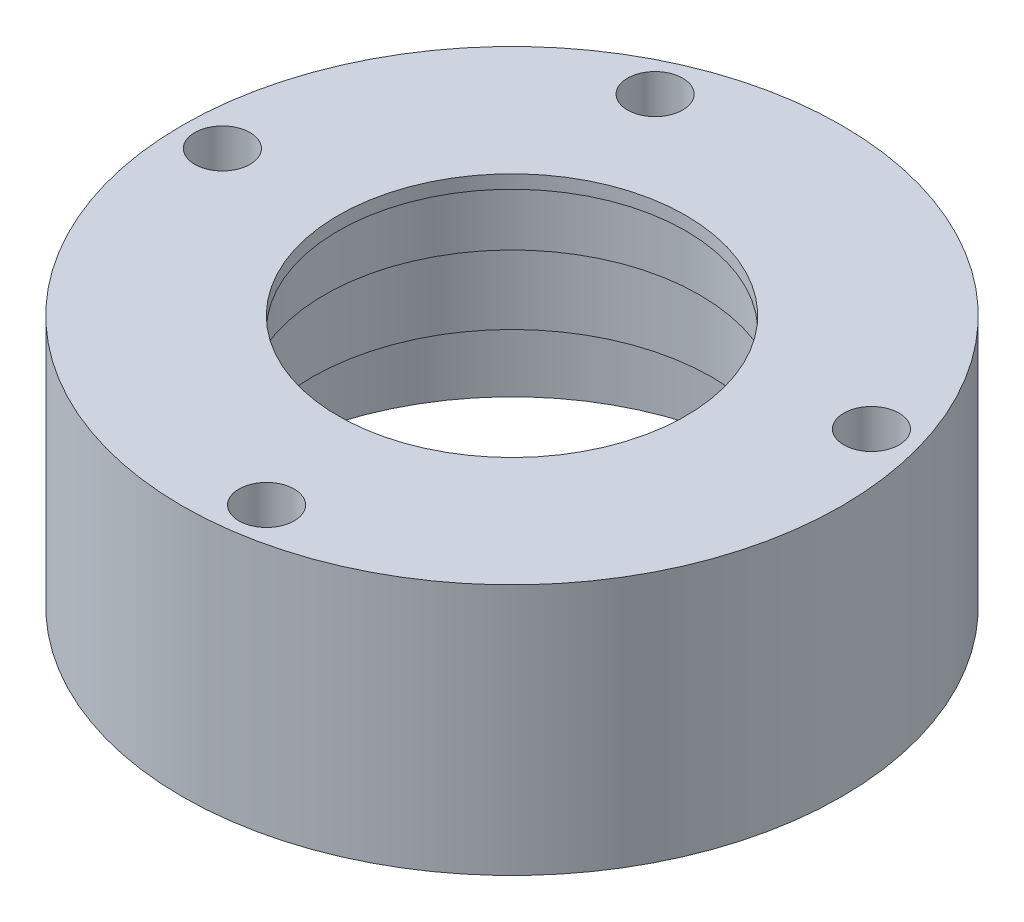
SolidWorks part; units mm, degrees
ref_plane "Front Plane" through (0, 0, 0) normal (0, 0, 1) x (1, 0, 0)
ref_plane "Top Plane" through (0, 0, 0) normal (0, 1, 0) x (1, 0, 0)
ref_plane "Right Plane" through (0, 0, 0) normal (1, 0, 0) x (0, 0, -1)
sketch "Sketch1" plane through (0, 0, 0) normal (0, 1, 0) x (1, 0, 0)
  circle A0 centre (0, 0) radius 37
  dimension "D1" = 74
extrude "Boss-Extrude1" add sketch "Sketch1" along normal blind 28.25
sketch "Sketch2" plane through (0, 0, 0) normal (0, 1, 0) x (1, 0, 0)
  circle A0 centre (0, 0) radius 28.8
  dimension "D1" = 57.6
extrude "Cut-Extrude1" cut sketch "Sketch2" along normal blind 11
sketch "Sketch3" plane through (0, 11, 0) normal (0, -1, 0) x (1, 0, 0)
  circle A0 centre (0, 0) radius 22.5
  dimension "D1" = 45
extrude "Cut-Extrude2" cut sketch "Sketch3" against normal blind 8.75
sketch "Sketch4" plane through (0, 19.75, 0) normal (0, -1, 0) x (1, 0, 0)
  circle A0 centre (0, 0) radius 21.05
  dimension "D1" = 42.1
extrude "Cut-Extrude3" cut sketch "Sketch4" against normal blind 7
sketch "Sketch5" plane through (0, 26.75, 0) normal (0, -1, 0) x (1, 0, 0)
  circle A0 centre (0, 0) radius 19.5
  dimension "D1" = 39
extrude "Cut-Extrude4" cut sketch "Sketch5" against normal through all
sketch "Sketch6" plane through (0, 0, 0) normal (0, 1, 0) x (1, 0, 0)
  line L0 (-15.5375, 0) -> (15.5375, 0) construction
  circle A0 centre (27, 0) radius 1.65
  dimension "D1" = 3.3
  dimension "D2" = 27
extrude "Cut-Extrude5" cut sketch "Sketch6" along normal blind 15.75
pattern_circular "CirPattern1" count 11 over 360 about axis through (0, 28.25, 0) along (0, -1, 0) of "Cut-Extrude5" reverse direction yes
sketch "Sketch7" plane through (0, 0, 0) normal (0, 1, 0) x (1, 0, 0)
  line L0 (0, 0) -> (43.5659, 0) construction
  line L1 (0, 0) -> (39.8091, 11.6863) construction
  line L2 (0, 0) -> (-18.3308, 40.1305) construction
  line L3 (0, 0) -> (-43.804, 0) construction
  line L4 (0, 0) -> (6.4033, -44.546) construction
  circle A0 centre (31.1841, 9.1543) radius 1.7
  circle A1 centre (-13.5033, 29.562) radius 1.7
  circle A2 centre (-32.5, 0) radius 1.7
  circle A3 centre (4.6242, -32.1693) radius 1.7
  dimension "D5" = 3.4
  dimension "D6" = 3.4
  dimension "D7" = 3.4
  dimension "D8" = 3.4
  dimension "D1" = 16.36
  dimension "D2" = 114.55
  dimension "D3" = 180
  dimension "D4" = 278.18
  dimension "D9" = 32.5
  dimension "D10" = 32.5
  dimension "D11" = 32.5
  dimension "D12" = 32.5
extrude "Cut-Extrude6" cut sketch "Sketch7" along normal through all
sketch "Sketch8" plane through (0, 28.25, 0) normal (0, 1, 0) x (1, 0, 0)
  circle A0 centre (31.1841, 9.1543) radius 3.1
  circle A1 centre (-13.5033, 29.562) radius 3.1
  circle A2 centre (-32.5, 0) radius 3.1
  circle A3 centre (4.6242, -32.1693) radius 3.1
  dimension "D1" = 6.2
  dimension "D2" = 6.2
  dimension "D3" = 6.2
  dimension "D4" = 6.2
extrude "Cut-Extrude7" cut sketch "Sketch8" against normal blind 16.25
equation "\"pin_circle_R\" = 27"
equation "\"ecc\" = 1.5"
equation "\"n_pins\" = 11"
equation "\"pin_d\" = 3"
equation "\"out_pin_R\" = 18.5"
equation "\"disc_clr\" = 0.1"
equation "\"seat_6803\" = 26.1"
equation "\"seat_6806\" = 42.1"
equation "\"disc_t\" = 5"
equation "\"out_hole_clr\" = 0.5"
equation "\"boss_17\" = 17.15"
equation "\"rotor_bolt_R\" = 10"
equation "\"m25_clr\" = 2.8"
equation "\"m25_head\" = 5"
equation "\"insert_hole\" = 4.4"
equation "\"csk\" = 0.6"
equation "\"peg_d\" = 3.0"
equation "\"plug_d\" = 8.6"
equation "\"peg_clr\" = 0.3"
equation "\"m3_clr\" = 3.4"
equation "\"m3_head\" = 6.2"
equation "\"pin_press\" = 3.2"
equation "\"pin_slip\" = 3.3"
equation "\"hub_30\" = 30.25"
equation "\"hub_short\" = 0.2"
equation "\"m3_tap\" = 2.8"
equation "\"rear_plate_t\" = 2"
equation "\"motor_ring\" = 40.4"
equation "\"D1@Sketch4\"=\"seat_6806\""
equation "\"D1@Sketch6\"=\"pin_slip\""
equation "\"D2@Sketch6\"=\"pin_circle_R\""
equation "\"D1@CirPattern1\"=\"n_pins\""
equation "\"D5@Sketch7\"=\"m3_clr\""
equation "\"D6@Sketch7\"=\"m3_clr\""
equation "\"D7@Sketch7\"=\"m3_clr\""
equation "\"D8@Sketch7\"=\"m3_clr\""
equation "\"D1@Sketch8\"=\"m3_head\""
equation "\"D2@Sketch8\"=\"m3_head\""
equation "\"D3@Sketch8\"=\"m3_head\""
equation "\"D4@Sketch8\"=\"m3_head\""
